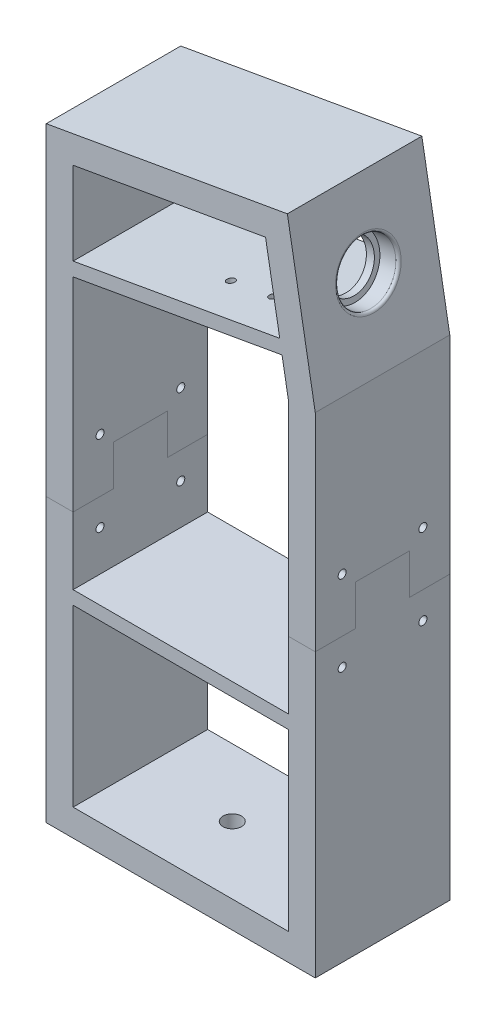
SolidWorks part; units mm, degrees
ref_plane "Front Plane" through (0, 0, 0) normal (0, 0, 1) x (1, 0, 0)
ref_plane "Top Plane" through (0, 0, 0) normal (0, 1, 0) x (1, 0, 0)
ref_plane "Right Plane" through (0, 0, 0) normal (1, 0, 0) x (0, 0, -1)
sketch "Sketch2" plane through (0, 0, 0) normal (0, 0, 1) x (1, 0, 0)
  line L6 (-50, 225.01) -> (-50, 0)
  line L8 (-50, 0) -> (50, 0)
  line L10 (-40, 216.619) -> (-40, 10)
  line L11 (-40, 10) -> (40, 10)
  line L12 (50, 0) -> (50, 182.01)
  line L13 (50, 182.01) -> (39.6312, 240.8144)
  line L14 (50, 182.01) -> (50, 266.0824) construction
  line L15 (39.6312, 240.8144) -> (-50, 225.01)
  line L16 (40, 10) -> (40, 181.1351)
  line L17 (40, 181.1351) -> (31.5196, 229.2298)
  line L18 (31.5196, 229.2298) -> (-40, 216.619)
  dimension "D1" = 182.01
  dimension "D2" = 100
  dimension "D3" = 10
  dimension "D4" = 225.01
  dimension "D6" = 10
extrude "Boss-Extrude1" add sketch "Sketch2" along normal blind 50
sketch "Sketch4" plane through (79.6179, 14.0388, 0) normal (0.9848, 0.1736, 0) x (0, 0, -1)
  line L0 (-25, 170.5625) -> (-25, 200.891) construction
  line L1 (-50, 170.5625) -> (0, 170.5625) construction
  line L2 (-50, 230.274) -> (0, 230.274) construction
  circle A0 centre (-25, 200.891) radius 11.025
  dimension "D1" = 22.05
  dimension "D2" = 29.383
extrude "Cut-Extrude1" cut sketch "Sketch4" against normal blind 7
sketch "Sketch5" plane through (72.7242, 12.8232, 0) normal (0.9848, 0.1736, 0) x (0, 0, -1)
  line L0 (-25, 211.916) -> (-25, 189.866) construction
  circle A0 centre (-25, 200.891) radius 11.025 construction
  circle A1 centre (-25, 200.891) radius 11.025 construction
  circle A2 centre (-25, 200.891) radius 9
  dimension "D1" = 18
extrude "Cut-Extrude2" cut sketch "Sketch5" against normal blind 7
sketch "Sketch7" plane through (0, 0, 50) normal (0, 0, 1) x (1, 0, 0)
  line L0 (40, 181.1351) -> (31.5196, 229.2298) construction
  line L5 (36.795, 199.3114) -> (37.6633, 194.3873)
  line L7 (-40, 180.6932) -> (-40, 185.7703)
  line L10 (36.795, 199.3114) -> (-40, 185.7703)
  line L11 (-40, 180.6932) -> (37.6633, 194.3873)
  line L12 (-40, 216.619) -> (-40, 10) construction
  line L13 (31.5196, 229.2298) -> (-40, 216.619) construction
  dimension "D1" = 30.38
  dimension "D3" = 5
extrude "Boss-Extrude2" add sketch "Sketch7" against normal blind 50
sketch "Sketch8" plane through (-50, 0, 0) normal (-1, 0, 0) x (0, 0, 1)
  line L0 (50, 225.01) -> (0, 225.01) construction
  line L1 (50, 225.01) -> (50, 0) construction
  line L3 (0, 225.01) -> (0, 0) construction
  line L4 (0, 204.1639) -> (50, 204.1639) construction
  circle A0 centre (25, 204.1639) radius 5
  dimension "D1" = 10
  dimension "D2" = 20.8461
extrude "Cut-Extrude3" cut sketch "Sketch8" against normal blind 10
sketch "Sketch9" plane through (123.2339, 209.4758, 0) normal (-0.1736, 0.9848, 0) x (-0.9848, -0.1736, 0)
  line L0 (76.8907, 25) -> (104.9692, 25) construction
  line L3 (104.9692, 34.6) -> (120.9692, 34.6) construction
  line L5 (76.8907, 50) -> (76.8907, 0) construction
  line L6 (104.9692, 25) -> (104.9692, 34.6) construction
  line L7 (104.9692, 25) -> (104.9692, 15.4) construction
  line L8 (120.9692, 34.6) -> (120.9692, 15.4) construction
  line L10 (120.9692, 15.4) -> (104.9692, 15.4) construction
  circle A0 centre (104.9692, 15.4) radius 1.485
  circle A1 centre (104.9692, 34.6) radius 1.485
  circle A2 centre (120.9692, 34.6) radius 1.485
  circle A3 centre (120.9692, 15.4) radius 1.485
  dimension "D1" = 28.0785
  dimension "D2" = 2.97
  dimension "D3" = 19.2
  dimension "D4" = 16
extrude "Cut-Extrude4" cut sketch "Sketch9" along normal up to next
sketch "Sketch10" plane through (0, 10, 0) normal (0, 1, 0) x (1, 0, 0)
  line L0 (50, -25) -> (24.131, -25) construction
  line L1 (-30.869, -50) -> (-30.869, 0) construction
  line L2 (50, -50) -> (50, 0) construction
  line L3 (-30, -25) -> (-5.8513, -25) construction
  circle A0 centre (-5.8513, -25) radius 3.425
  circle A1 centre (24.131, -25) radius 3.425
  dimension "D1" = 6.85
  dimension "D2" = 6.85
  dimension "D3" = 25.0177
  dimension "D4" = 55
extrude "Cut-Extrude5" cut sketch "Sketch10" against normal blind 10
sketch "Sketch11" plane through (0, 0, 50) normal (0, 0, 1) x (1, 0, 0)
  line L0 (-40, 75) -> (40, 75)
  line L3 (40, 75) -> (40, 80)
  line L4 (40, 80) -> (-40, 80)
  line L5 (-40, 80) -> (-40, 75)
  line L6 (-40, 180.6932) -> (-40, 10) construction
  line L7 (40, 10) -> (40, 181.1351) construction
  dimension "D1" = 5
  dimension "D2" = 75
extrude "Boss-Extrude3" add sketch "Sketch11" against normal blind 50
fillet "Fillet1" radius 1 1 edges at (42.819, 222.7353, 25) type face fillet first side face at (35.9254, 221.5198, 25) second side face at (42.819, 222.7353, 25)
sketch "Sketch14" plane through (-50, 0, 0) normal (-1, 0, 0) x (0, 0, 1)
  line L0 (0, 0) -> (0, 105) construction
  line L1 (0, 225.01) -> (0, 0) construction
  line L2 (0, 105) -> (50, 105) construction
  line L3 (50, 225.01) -> (50, 0) construction
  line L4 (50, 105) -> (50, 125) construction
  line L5 (50, 105) -> (50, 95) construction
  line L6 (50, 125) -> (40, 125) construction
  line L7 (50, 95) -> (40, 95) construction
  line L8 (25, 0) -> (25, 105) construction
  line L10 (50, 0) -> (0, 0) construction
  circle A0 centre (40, 125) radius 1.5
  circle A1 centre (40, 95) radius 1.5
  circle A2 centre (10, 95) radius 1.5
  circle A3 centre (10, 125) radius 1.5
  dimension "D1" = 3
  dimension "D2" = 3
  dimension "D3" = 95
  dimension "D4" = 125
  dimension "D5" = 15
extrude "Cut-Extrude6" cut sketch "Sketch14" against normal through all
sketch "Sketch15" plane through (-50, 0, 0) normal (-1, 0, 0) x (0, 0, 1)
  line L0 (0, 0) -> (0, 105) construction
  line L1 (0, 225.01) -> (0, 0) construction
  line L2 (0, 105) -> (15, 105)
  line L3 (15, 105) -> (15, 120)
  line L4 (15, 120) -> (35, 120)
  line L5 (35, 120) -> (35, 105)
  line L6 (35, 105) -> (50, 105)
  line L7 (50, 225.01) -> (50, 0) construction
  line L8 (50, 0) -> (0, 0) construction
  dimension "D1" = 15
  dimension "D2" = 35
  dimension "D3" = 15
  dimension "D4" = 105
  dimension "D5" = 105
split "Split1" trim tools "Sketch15" bodies to split 116 resulting bodies 117 118
